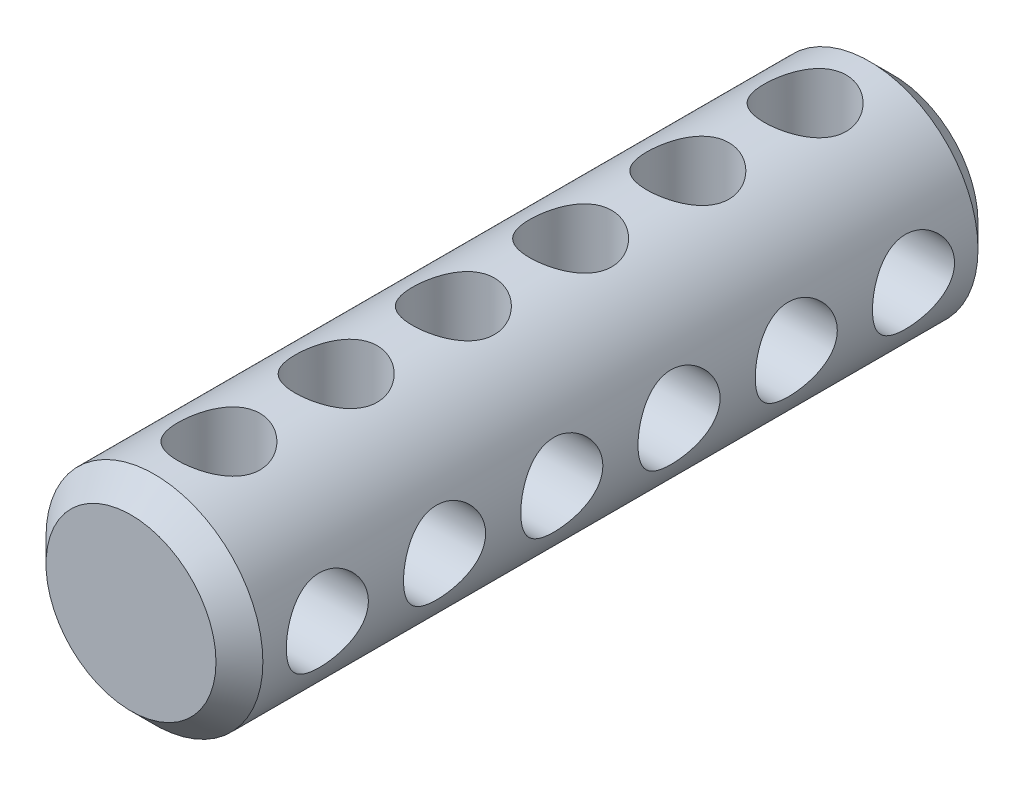
SolidWorks part; units mm, degrees
ref_plane "Спереди" through (0, 0, 0) normal (0, 0, 1) x (1, 0, 0)
ref_plane "Сверху" through (0, 0, 0) normal (0, 1, 0) x (1, 0, 0)
ref_plane "Справа" through (0, 0, 0) normal (1, 0, 0) x (0, 0, -1)
sketch "Эскиз1" plane through (0, 0, 0) normal (0, 0, 1) x (1, 0, 0)
  circle A0 centre (0, 0) radius 9.25
  dimension "D1" = 18.5
extrude "Бобышка-Вытянуть1" add sketch "Эскиз1" along normal blind 65
chamfer "Фаска1" distance 2 angle 45 2 edges at (9.25, 0, 0) (9.25, 0, 65)
sketch "Эскиз2" plane through (0, 0, 0) normal (0, 1, 0) x (1, 0, 0)
  line L0 (0, 0) -> (0, -65) construction
  line L1 (7.25, 0) -> (-7.25, 0) construction
  line L2 (-7.25, -65) -> (7.25, -65) construction
  circle A0 centre (0, -7.5) radius 3.5
  circle A1 centre (0, -17.5) radius 3.5
  circle A2 centre (0, -27.5) radius 3.5
  circle A3 centre (0, -37.5) radius 3.5
  circle A4 centre (0, -47.5) radius 3.5
  circle A5 centre (0, -57.5) radius 3.5
  dimension "D1" = 7
  dimension "D2" = 7.5
  dimension "D4" = 7.5
  dimension "D3" = 6
extrude "Вырез-Вытянуть1" cut sketch "Эскиз2" against normal blind 65 and the other way blind 65
pattern_circular "Круговой массив1" count 2 every 90 about axis through (0, 0, 65) along (0, 0, -1) of "Вырез-Вытянуть1"
